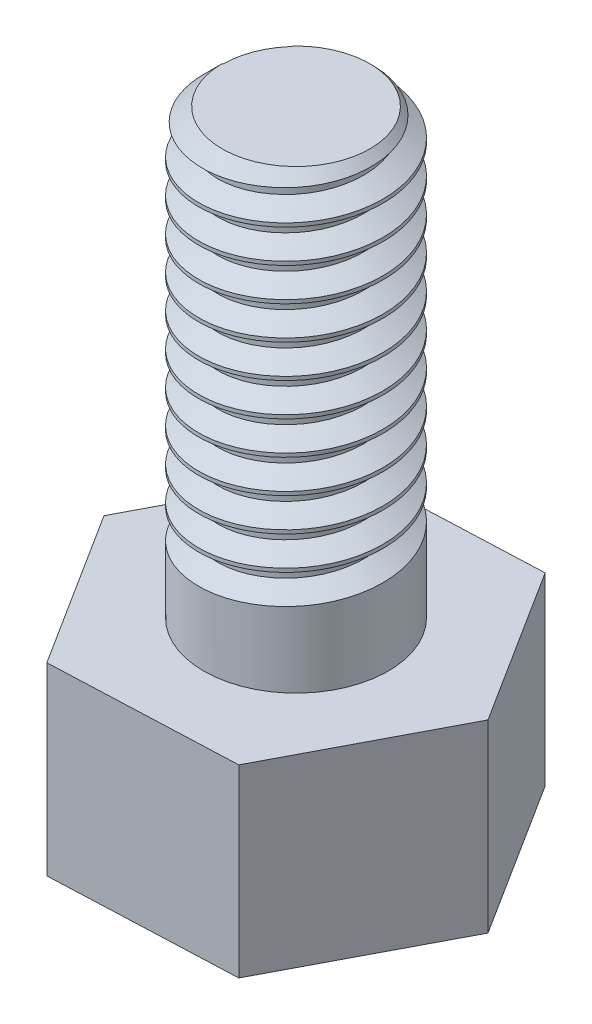
SolidWorks part; units mm, degrees
ref_plane "Ön Düzlem" through (0, 0, 0) normal (0, 0, 1) x (1, 0, 0)
ref_plane "Üst Düzlem" through (0, 0, 0) normal (0, 1, 0) x (1, 0, 0)
ref_plane "Sağ Düzlem" through (0, 0, 0) normal (1, 0, 0) x (0, 0, -1)
sketch "Çizim1" plane through (0, 0, 0) normal (0, 1, 0) x (1, 0, 0)
  line L1 (2.6752, -4.2241) -> (4.9958, 0.2047)
  line L2 (4.9958, 0.2047) -> (2.3206, 4.4289)
  line L3 (2.3206, 4.4289) -> (-2.6752, 4.2241)
  line L4 (-2.6752, 4.2241) -> (-4.9958, -0.2047)
  line L5 (-4.9958, -0.2047) -> (-2.3206, -4.4289)
  line L6 (-2.3206, -4.4289) -> (2.6752, -4.2241)
  circle A0 centre (0, 0) radius 5 construction
extrude "Yükseklik-Ekstrüzyon1" add sketch "Çizim1" along normal blind 5
sketch "Çizim2" plane through (0, 5, 0) normal (0, 1, 0) x (1, 0, 0)
  circle A0 centre (0, 0) radius 2.5
  dimension "D1" = 5
extrude "Yükseklik-Ekstrüzyon2" add sketch "Çizim2" along normal blind 12
chamfer "Pah1" distance 0.5 angle 45 1 edges at (0, 17, 2.5)
sketch "Çizim3" plane through (0, 17, 0) normal (0, 1, 0) x (1, 0, 0)
  circle A0 centre (0, 0) radius 2.5 construction
  circle A1 centre (0, 0) radius 2.5
curve "Helis/Spiral1" pitch 0.9 height 10 turns 11.1111
ref_plane "Düzlem1" through (-2.5, 17, 0) normal (0, -0.0572, -0.9984) x (-1, 0, 0)
sketch "Çizim4" plane through (-2.5, 17, 0) normal (0, -0.0572, -0.9984) x (-1, 0, 0)
  line L0 (0, 0) -> (-0.302, 0) construction
  line L1 (0, 0.4) -> (0, -0.4)
  line L2 (0, -0.4) -> (-0.5196, -0.1)
  line L3 (-0.5196, -0.1) -> (-0.5196, 0.1)
  line L4 (-0.5196, 0.1) -> (0, 0.4)
  point P5 (0, 0)
  point P7 (-0.5196, 0)
  dimension "D1" = 0.8
  dimension "D2" = 0.2
  dimension "D3" = 60
sweep "Kes-Süpür3" cut profiles "Çizim4" path "Helis/Spiral1"
